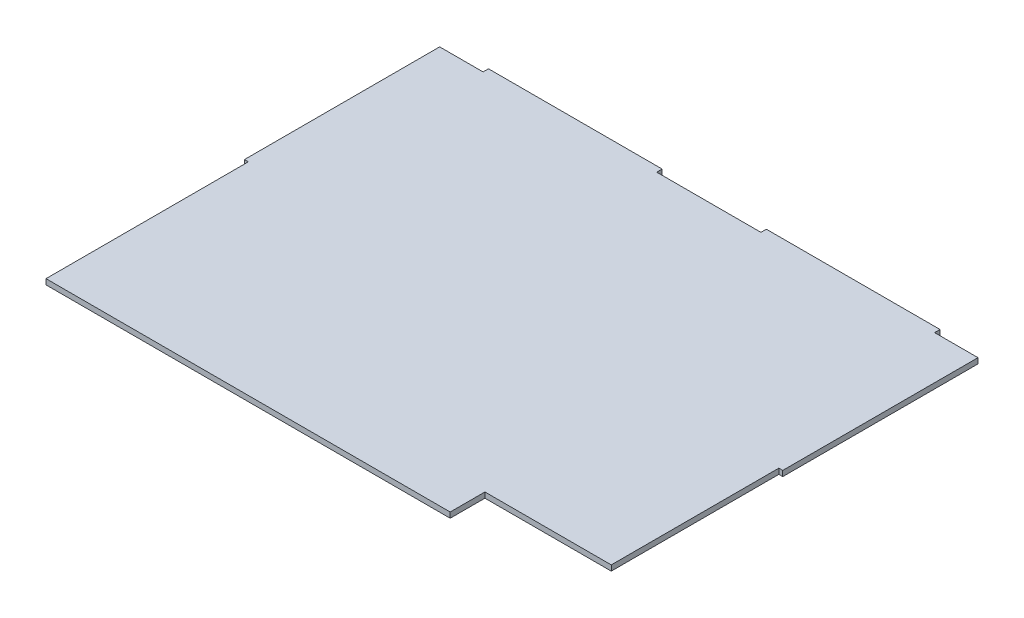
SolidWorks part; units mm, degrees
material "Custom Plastic"
ref_plane "X-Y Datum" through (0, 0, 0) normal (0, 0, 1) x (1, 0, 0)
ref_plane "X-Z Datum" through (0, 0, 0) normal (0, 1, 0) x (1, 0, 0)
ref_plane "Y-Z Datum" through (0, 0, 0) normal (1, 0, 0) x (0, 0, -1)
sketch "Sketch1" plane through (0, 0, 0) normal (0, 0, 1) x (1, 0, 0)
  line L1 (-157.4823, -1.5875) -> (157.4823, -1.5875)
  line L2 (-157.4823, -1.5875) -> (-157.4823, 1.5875)
  line L3 (-157.4823, 1.5875) -> (157.4823, 1.5875)
  line L4 (157.4823, -1.5875) -> (157.4823, 1.5875)
  line L5 (-157.4823, -1.5875) -> (157.4823, 1.5875) construction
  line L6 (-157.4823, 1.5875) -> (157.4823, -1.5875) construction
  point P0 (0, 0)
  dimension "D1" = 314.9646
  dimension "D2" = 3.175
extrude "Boss-Extrude1" add sketch "Sketch1" along normal blind 235.775
sketch "Sketch3" plane through (0, 0, 0) normal (0, 0, -1) x (-1, 0, 0)
  line L0 (-157.4823, 0) -> (-81.2823, 0) construction
  line L1 (-157.4823, -1.5875) -> (-157.4823, 1.5875) construction
  line L2 (-157.4823, 1.5875) -> (157.4823, 1.5875) construction
  line L3 (-132.0823, -1.5875) -> (-30.4823, -1.5875)
  line L4 (-132.0823, -1.5875) -> (-132.0823, 1.5875)
  line L5 (-132.0823, 1.5875) -> (-30.4823, 1.5875)
  line L6 (-30.4823, -1.5875) -> (-30.4823, 1.5875)
  line L7 (-132.0823, -1.5875) -> (-30.4823, 1.5875) construction
  line L8 (-132.0823, 1.5875) -> (-30.4823, -1.5875) construction
  line L14 (-157.4823, 1.5875) -> (-132.0823, 1.5875)
  line L15 (-157.4823, 1.5875) -> (-157.4823, -1.5875)
  line L16 (-157.4823, -1.5875) -> (-132.0823, -1.5875)
  line L17 (-132.0823, 1.5875) -> (-132.0823, -1.5875)
  line L19 (-30.4823, 1.5875) -> (-30.4823, -1.5875)
  line L20 (0, 43.0151) -> (0, -43.0151) construction
  line L21 (30.4823, -1.5875) -> (30.4823, 1.5875)
  line L22 (132.0823, -1.5875) -> (132.0823, 1.5875)
  line L23 (132.0823, 1.5875) -> (30.4823, 1.5875)
  line L24 (132.0823, -1.5875) -> (30.4823, 1.5875) construction
  line L25 (132.0823, -1.5875) -> (30.4823, -1.5875)
  line L26 (132.0823, 1.5875) -> (30.4823, -1.5875) construction
  line M2 (-157.4823, 1.5875) -> (-157.4823, -1.5875)
  line M3 (-157.4823, -1.5875) -> (157.4823, -1.5875)
  line M4 (157.4823, -1.5875) -> (157.4823, 1.5875)
  line M5 (157.4823, 1.5875) -> (-157.4823, 1.5875)
  dimension "D1" = 76.2
  dimension "D2" = 101.6
extrude "Cut-Extrude1" cut sketch "Sketch3" against normal blind 3.175 contours L4 M3 M5 M2 | L6 M3 M5 | M3 M4 M5 region at (144.7823, 0, 0) region at (0, 0, 0) region at (-144.7823, 0, 0)
sketch "Sketch5" plane through (0, 1.5875, 0) normal (0, 1, 0) x (1, 0, 0)
  line L1 (-157.4823, -235.775) -> (-155.1963, -235.775)
  line L3 (-157.4823, -235.775) -> (-157.4823, -117.411)
  line L5 (-157.4823, -117.411) -> (-155.1963, -117.411)
  line L6 (-155.1963, -235.775) -> (-155.1963, -117.411)
  line M11 (-157.4823, -3.175) -> (-157.4823, -235.775)
  line M12 (-157.4823, -235.775) -> (157.4823, -235.775)
  dimension "D1" = 118.364
  dimension "D2" = 2.286
extrude "Cut-Extrude2" cut sketch "Sketch5" against normal blind 3.175 and the other way through all contours M12 M11 region at (-156.3393, 1.5875, 176.593)
mirror "Mirror1" about plane through (0, 0, 0) normal (1, 0, 0) of "Cut-Extrude2"
sketch "Sketch6" plane through (0, 1.5875, 0) normal (0, 1, 0) x (1, 0, 0)
  line L6 (-157.4823, -215.455) -> (-81.2823, -215.455)
  line L7 (-157.4823, -215.455) -> (-157.4823, -235.775)
  line L8 (-157.4823, -235.775) -> (-81.2823, -235.775)
  line L9 (-81.2823, -215.455) -> (-81.2823, -235.775)
  line L10 (155.1963, -235.775) -> (-155.1963, -235.775) construction
  line L11 (-157.4823, -117.411) -> (-157.4823, -3.175) construction
  line L13 (155.1963, -235.775) -> (-81.2823, -235.775)
  line L14 (155.1963, -235.775) -> (155.1963, -215.455)
  line L15 (155.1963, -215.455) -> (-81.2823, -215.455)
  line L16 (-81.2823, -235.775) -> (-81.2823, -215.455)
  line M18 (-155.1963, -117.411) -> (-155.1963, -235.775)
  line M19 (-155.1963, -235.775) -> (155.1963, -235.775)
  dimension "D1" = 76.2
  dimension "D2" = 20.32
extrude "Cut-Extrude4" [suppressed] cut sketch "Sketch6" against normal through all contours L9 L6 M18 M19
sketch "Sketch7" [suppressed] plane through (0, 1.5875, 0) normal (0, 1, 0) x (1, 0, 0)
  line L1 (-81.2823, -215.455) -> (155.1963, -215.455)
  line L2 (-81.2823, -215.455) -> (-81.2823, -235.775)
  line L3 (-81.2823, -235.775) -> (155.1963, -235.775)
  line L4 (155.1963, -215.455) -> (155.1963, -235.775)
extrude "Cut-Extrude5" [suppressed] cut sketch "Sketch7" against normal through all
sketch "Sketch8" plane through (0, 1.5875, 0) normal (0, 1, 0) x (1, 0, 0)
  line L0 (155.1963, -235.775) -> (-155.1963, -235.775) construction
  line L1 (157.4823, -215.455) -> (81.2823, -215.455)
  line L2 (157.4823, -215.455) -> (157.4823, -235.775)
  line L3 (157.4823, -235.775) -> (81.2823, -235.775)
  line L4 (81.2823, -215.455) -> (81.2823, -235.775)
  line L5 (157.4823, -117.411) -> (157.4823, -3.175) construction
  dimension "D1" = 20.32
  dimension "D2" = 76.2
extrude "Cut-Extrude6" cut sketch "Sketch8" against normal through all
